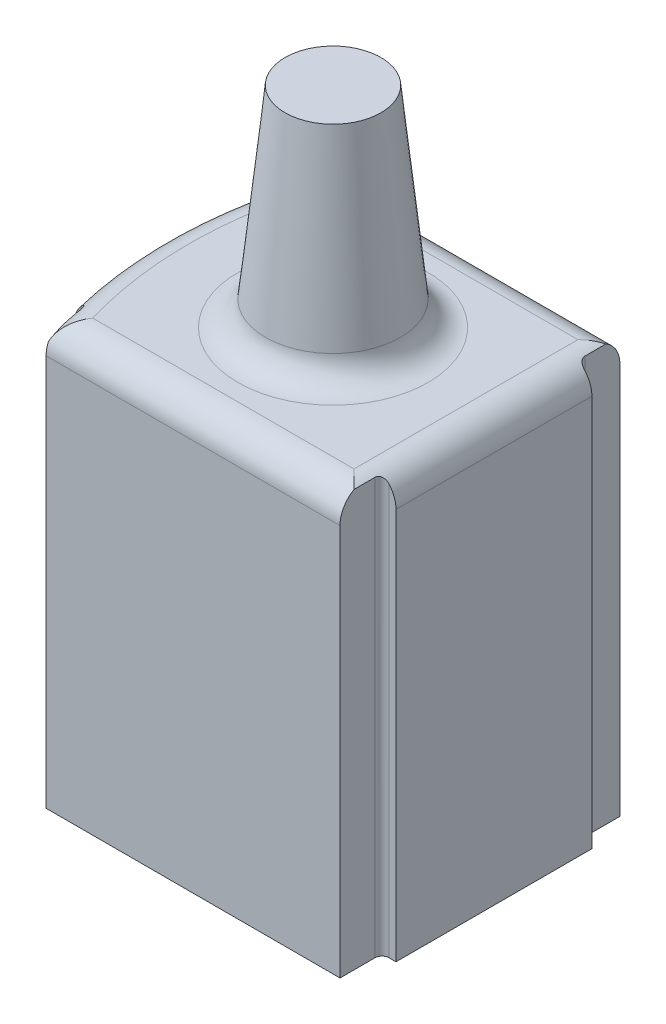
SolidWorks part; units mm, degrees
material "PET"
ref_plane "Alzado" through (0, 0, 0) normal (0, 0, 1) x (1, 0, 0)
ref_plane "Planta" through (0, 0, 0) normal (0, 1, 0) x (1, 0, 0)
ref_plane "Vista lateral" through (0, 0, 0) normal (1, 0, 0) x (0, 0, -1)
sketch "Croquis1" plane through (0, 0, 0) normal (0, 1, 0) x (1, 0, 0)
  line L1 (0, 0) -> (21, 0)
  line L2 (0, 0) -> (0, 2.5)
  line L3 (0, 20) -> (21, 20)
  line L4 (22, 3) -> (22, 17)
  line L8 (22, 17) -> (21.5, 17)
  line L9 (21, 17.5) -> (21, 20)
  line L10 (22, 3) -> (21.5, 3)
  line L11 (21, 2.5) -> (21, 0)
  line L12 (10.5, 20) -> (10.5, 0) construction
  line L13 (0, 2.5) -> (0, 0)
  line L14 (-1, 3) -> (-0.5, 3)
  line L15 (-1, 17) -> (-0.5, 17)
  line L16 (0, 17.5) -> (0, 20)
  line L17 (0, 17.5) -> (0, 20)
  arc A6 (22, 17) -> (22, 3) centre (-7.1719, 10) cw
  arc A7 (21.5, 17) -> (21, 17.5) centre (21.5, 17.5) cw
  arc A8 (21, 2.5) -> (21.5, 3) centre (21.5, 2.5) cw
  arc A9 (0, 2.5) -> (-0.5, 3) centre (-0.5, 2.5) ccw
  arc A10 (-1, 17) -> (-1, 3) centre (28.1719, 10) ccw
  arc A11 (-0.5, 17) -> (0, 17.5) centre (-0.5, 17.5) ccw
  point P24 (22.8281, 10)
  dimension "D5" = 30
  dimension "D8" = 0.5
  dimension "D9" = 0.5
  dimension "D6" = 14
  dimension "D7" = 10
extrude "Saliente-Extruir1" add sketch "Croquis1" along normal blind 30 contours L12 L3 L16 A11 L15 A10 L14 A9 L2 L1 | L3 L12 L1 L11 A8 L10 L4 L8 A7 L9 region at (4.6803, 0, -10) region at (16.1118, 0, -10)
sketch "Croquis2" plane through (0, 30, 0) normal (0, 1, 0) x (1, 0, 0)
  line L0 (10.5, 20) -> (10.5, 0) construction
  line L1 (0, 20) -> (21, 20) construction
  line L2 (0, 0) -> (21, 0) construction
  circle A0 centre (10.5, 10) radius 5
  dimension "D1" = 10
extrude "Saliente-Extruir2" add sketch "Croquis2" along normal blind 15 draft 6
fillet "Redondeo1" radius 2 4 edges at (10.5, 30, -20) (10.5, 30, 0) (22, 30, -10) (-1.8281, 30, -10)
fillet "Redondeo2" radius 2 1 edges at (10.5, 30, -5)
